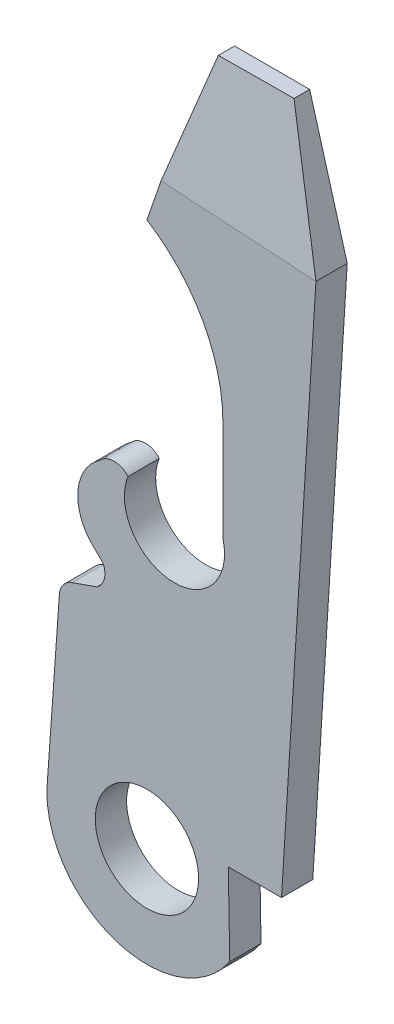
SolidWorks part; units mm, degrees
material "Plain Carbon Steel"
ref_plane "Front Plane" through (0, 0, 0) normal (0, 0, 1) x (1, 0, 0)
ref_plane "Top Plane" through (0, 0, 0) normal (0, 1, 0) x (1, 0, 0)
ref_plane "Right Plane" through (0, 0, 0) normal (1, 0, 0) x (0, 0, -1)
sketch "Sketch1" plane through (0, 0, 0) normal (0, 0, 1) x (1, 0, 0)
  line L0 (14.7211, 33.1224) -> (73.6054, 33.1224) construction
  line L1 (48.6367, 40.0161) -> (47.2397, 17.6641)
  line L2 (47.2397, 17.6641) -> (45.0807, 17.6641)
  line L3 (44.0647, 45.3668) -> (47.1127, 45.3668)
  line L4 (47.1127, 45.3668) -> (48.6367, 40.0161)
  line L5 (44.0647, 45.3668) -> (41.7787, 38.7461)
  line L6 (44.8632, 33.1581) -> (44.8632, 29.0941)
  line L7 (45.0807, 17.6641) -> (45.1388, 14.3621)
  line L8 (38.2227, 23.7601) -> (37.7147, 16.6481)
  line L9 (38.7307, 24.4785) -> (39.7467, 24.8377)
  line L10 (39.4927, 26.3001) -> (40.0007, 25.7921)
  arc A1 (41.012, 29.3481) -> (44.8632, 29.0941) centre (42.8957, 28.5861) ccw
  arc A2 (39.8761, 29.3481) -> (39.4927, 26.3001) centre (41.0043, 27.6581) ccw
  arc A3 (41.012, 29.3481) -> (39.8761, 29.3481) centre (40.444, 28.8401) ccw
  arc A4 (39.7467, 24.8377) -> (40.0007, 25.7921) centre (39.3129, 25.4641) ccw
  arc A5 (38.7307, 24.4785) -> (38.2227, 23.7601) centre (38.9847, 23.7601) ccw
  arc A6 (37.7147, 16.6481) -> (45.1388, 14.3621) centre (41.7787, 16.6481) ccw
  arc A7 (44.8632, 33.1581) -> (41.7787, 38.7461) centre (38.2592, 33.1581) ccw
  point P14 (0, 0)
  point P20 (0, 0)
  point P22 (0, 0)
  point P24 (0, 0)
  point P30 (0, 0)
  point P31 (0, 0)
  point P32 (0, 0)
  point P33 (0, 0)
  point P34 (0, 0)
  point P35 (0, 0)
  point P36 (0, 0)
  point P37 (0, 0)
  point P38 (0, 0)
  point P39 (0, 0)
  point P40 (0, 0)
  dimension "D6" = 23.368
  dimension "D7" = 6.858
  dimension "D8" = 5.334
  dimension "D9" = 22.098
  dimension "D10" = 4.064
  dimension "D11" = 6.604
  dimension "D13" = 2.032
  dimension "D16" = 0.762
  dimension "D18" = 2.032
  dimension "D21" = 0.762
  dimension "D24" = 0.762
  dimension "D1" = 9.525
  dimension "D2" = 28.7187
  dimension "D3" = 1.016
  dimension "D4" = 2.286
  dimension "D5" = 3.302
  dimension "D12" = 16.51
  dimension "D14" = 12.446
  dimension "D15" = 12.7
  dimension "D17" = 12.7
  dimension "D19" = 2.286
  dimension "D20" = 1.778
  dimension "D22" = 2.032
  dimension "D23" = 3.048
  dimension "D25" = 3.556
  dimension "D26" = 7.112
  dimension "D27" = 9.144
  dimension "D28" = 9.652
  dimension "D29" = 11.938
  dimension "D30" = 12.192
  dimension "D31" = 2.286
extrude "Boss-Extrude1" add sketch "Sketch1" along normal blind 1.27
sketch "Sketch2" plane through (0, 0, 1.27) normal (0, 0, 1) x (1, 0, 0)
  circle A0 centre (41.7787, 16.6481) radius 2.0955
  dimension "D1" = 4.191
extrude "Cut-Extrude1" cut sketch "Sketch2" against normal through all
sketch "Sketch3" plane through (45.9562, -2.8723, 0) normal (0.9981, -0.0624, 0) x (0, 0, -1)
  line L2 (-0.635, 48.2172) -> (-1.27, 42.972)
  line L3 (-1.27, 42.972) -> (-1.27, 48.2172)
  line L4 (-1.27, 48.2172) -> (-0.635, 48.2172)
  dimension "D1" = 0.635
extrude "Cut-Extrude2" cut sketch "Sketch3" against normal through all
